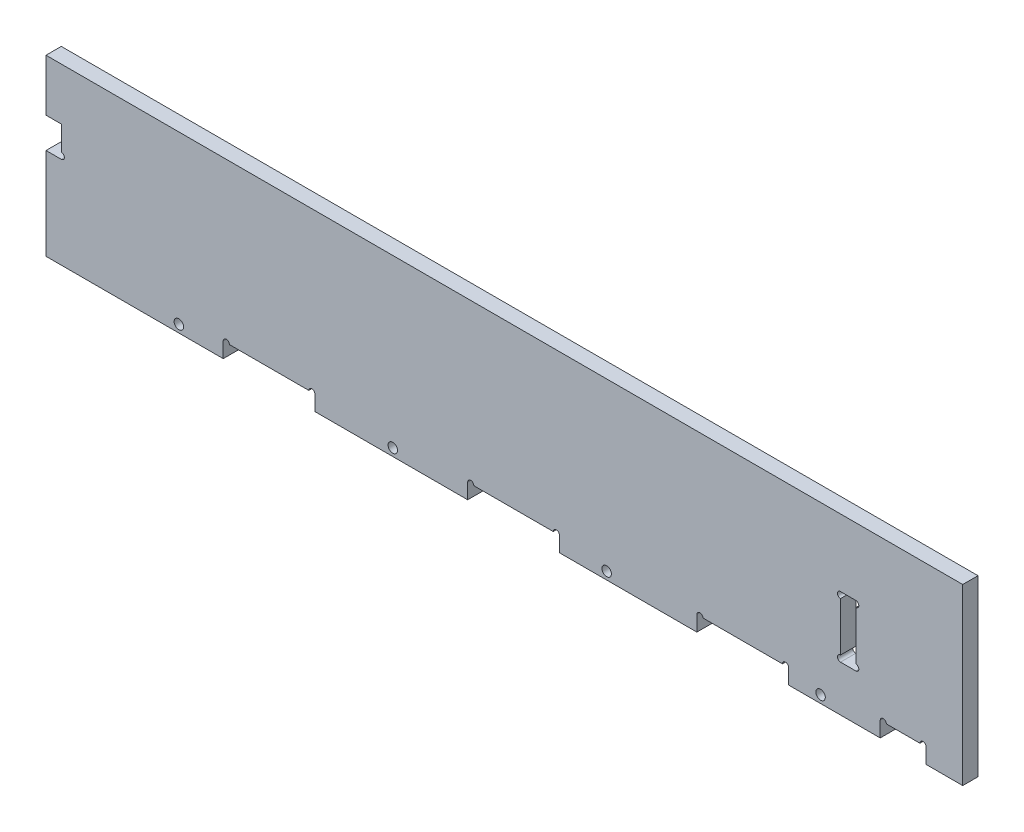
SolidWorks part; units mm, degrees
material "사용자정의 플라스틱"
ref_plane "정면" through (0, 0, 0) normal (0, 0, 1) x (1, 0, 0)
ref_plane "윗면" through (0, 0, 0) normal (0, 1, 0) x (1, 0, 0)
ref_plane "우측면" through (0, 0, 0) normal (1, 0, 0) x (0, 0, -1)
sketch "스케치1" plane through (0, 0, 0) normal (0, 0, 1) x (1, 0, 0)
  line L1 (0, 0) -> (300, 0)
  line L2 (0, 0) -> (0, 57)
  line L3 (0, 57) -> (300, 57)
  line L4 (300, 0) -> (300, 57)
  dimension "D1" = 57
  dimension "D2" = 300
extrude "보스-돌출1" add sketch "스케치1" along normal blind 5
sketch "스케치2" plane through (0, 0, 5) normal (0, 0, 1) x (1, 0, 0)
  line L0 (0, 57) -> (0, 0) construction
  line L1 (5, 40) -> (0, 40)
  line L2 (5, 40) -> (5, 30)
  line L3 (5, 30) -> (0, 30)
  line L4 (0, 40) -> (0, 30)
  line L5 (5, 30) -> (0, 30) construction
  line L6 (0, 0) -> (300, 0) construction
  line L7 (58, 5) -> (88, 5)
  line L8 (58, 5) -> (58, 0)
  line L9 (58, 0) -> (88, 0)
  line L10 (88, 5) -> (88, 0)
  line L11 (88, 5) -> (88, 0) construction
  line L12 (168, 5) -> (168, 0) construction
  line L13 (168, 0) -> (138, 0)
  line L14 (168, 0) -> (168, 5)
  line L15 (168, 5) -> (138, 5)
  line L16 (138, 0) -> (138, 5)
  line L17 (243, 5) -> (243, 0) construction
  line L18 (243, 0) -> (213, 0)
  line L19 (243, 0) -> (243, 5)
  line L20 (243, 5) -> (213, 5)
  line L21 (213, 0) -> (213, 5)
  line L22 (288, 5) -> (288, 0) construction
  line L23 (288, 0) -> (273, 0)
  line L24 (288, 0) -> (288, 5)
  line L25 (288, 5) -> (273, 5)
  line L26 (273, 0) -> (273, 5)
  line L28 (260, 35) -> (265, 35)
  line L29 (260, 35) -> (260, 15)
  line L30 (260, 15) -> (265, 15)
  line L31 (265, 35) -> (265, 15)
extrude "컷-돌출1" cut sketch "스케치2" against normal blind 5
sketch "스케치3" plane through (0, 0, 5) normal (0, 0, 1) x (1, 0, 0)
  line L0 (265, 35) -> (260, 35) construction
  line L1 (260, 15) -> (265, 15) construction
  line L4 (243, 5) -> (213, 5) construction
  line L5 (88, 5) -> (58, 5) construction
  line L6 (168, 5) -> (138, 5) construction
  line L7 (5, 30) -> (5, 40) construction
  line L8 (288, 5) -> (273, 5) construction
  line L9 (273, 5) -> (273, 0) construction
  line L10 (288, 0) -> (288, 5) construction
  circle A0 centre (274, 5) radius 1
  circle A1 centre (287, 5) radius 1
  circle A2 centre (260, 16) radius 1
  circle A3 centre (265, 16) radius 1
  circle A4 centre (265, 34) radius 1
  circle A5 centre (260, 34) radius 1
  circle A6 centre (214, 5) radius 1
  circle A7 centre (242, 5) radius 1
  circle A8 centre (87, 5) radius 1
  circle A9 centre (139, 5) radius 1
  circle A10 centre (167, 5) radius 1
  circle A11 centre (5, 31) radius 1
  circle A13 centre (59, 5) radius 1
  dimension "D1" = 2
  dimension "D2" = 2
extrude "컷-돌출2" cut sketch "스케치3" against normal blind 5
sketch "스케치4" plane through (0, 0, 0) normal (0, 0, -1) x (-1, 0, 0)
  line L0 (-45.0287, 2.5) -> (-41.9287, 2.5) construction
  line L3 (-45.0287, 5) -> (-45.0287, 0) construction
  line L6 (-41.9287, 5) -> (-41.9287, 0) construction
  line L9 (-115.0287, 2.5) -> (-111.9287, 2.5) construction
  line L10 (-115.0287, 5) -> (-115.0287, 0) construction
  line L11 (-111.9287, 5) -> (-111.9287, 0) construction
  line L12 (-185.0287, 2.5) -> (-181.9287, 2.5) construction
  line L13 (-185.0287, 5) -> (-185.0287, 0) construction
  line L14 (-181.9287, 5) -> (-181.9287, 0) construction
  line L15 (-255.0287, 2.5) -> (-251.9287, 2.5) construction
  line L16 (-255.0287, 5) -> (-255.0287, 0) construction
  line L17 (-251.9287, 5) -> (-251.9287, 0) construction
  circle A0 centre (-253.4787, 2.5) radius 1.55
  circle A1 centre (-183.4787, 2.5) radius 1.55
  circle A2 centre (-113.4787, 2.5) radius 1.55
  circle A3 centre (-43.4787, 2.5) radius 1.55
extrude "컷-돌출3" cut sketch "스케치4" against normal blind 10
